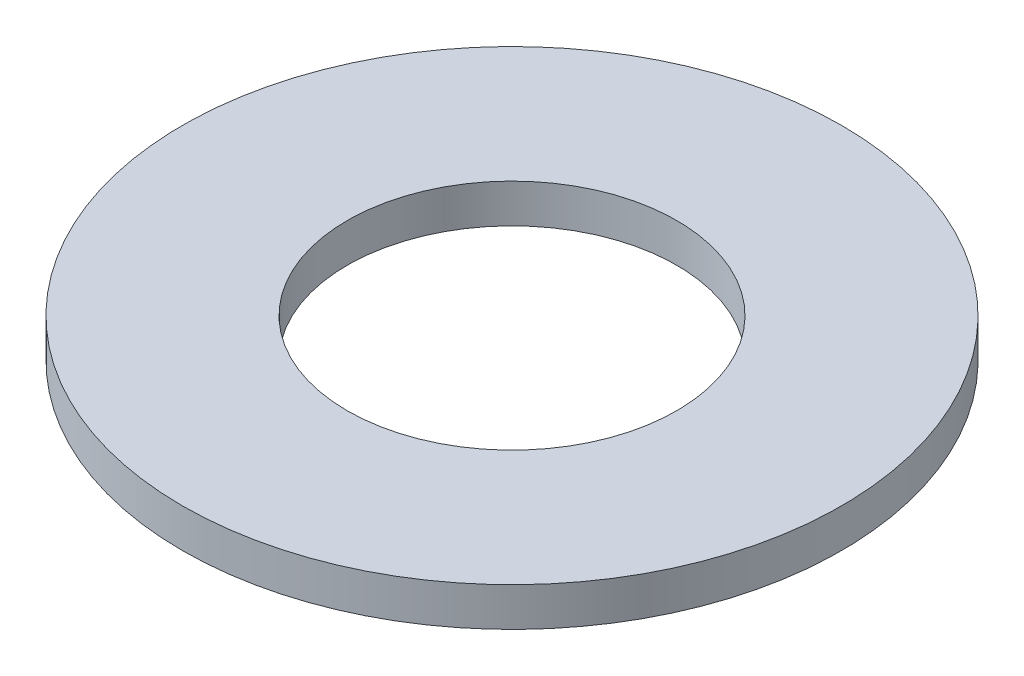
SolidWorks part; units mm, degrees
ref_plane "Front Plane" through (0, 0, 0) normal (0, 0, 1) x (1, 0, 0)
ref_plane "Top Plane" through (0, 0, 0) normal (0, 1, 0) x (1, 0, 0)
ref_plane "Right Plane" through (0, 0, 0) normal (1, 0, 0) x (0, 0, -1)
sketch "Sketch1" plane through (0, 0, 0) normal (0, 1, 0) x (1, 0, 0)
  circle A0 centre (0, 0) radius 85
  dimension "FLANGE_OD" = 170
extrude "Boss-Extrude1" add sketch "Sketch1" along normal blind 10
sketch "Sketch2" plane through (0, 0, 0) normal (0, 1, 0) x (1, 0, 0)
  circle A0 centre (0, 0) radius 42.5
  dimension "BORE_D" = 85
extrude "Cut-Extrude1" cut sketch "Sketch2" along normal through all
sketch "Sketch3" plane through (0, 10, 0) normal (0, 1, 0) x (1, 0, 0)
  circle A0 centre (0, 0) radius 30.0135 construction
  circle A1 centre (-30.0135, 0) radius 7.4148
  dimension "BOLT_D" = 14.8296
  dimension "BOLT_PCD" = 60.0269
extrude "Cut-Extrude2" cut sketch "Sketch3" against normal blind 8.7815 rebuild error yes
pattern_circular "CirPattern1" count 5 over 360 rebuild error yes
